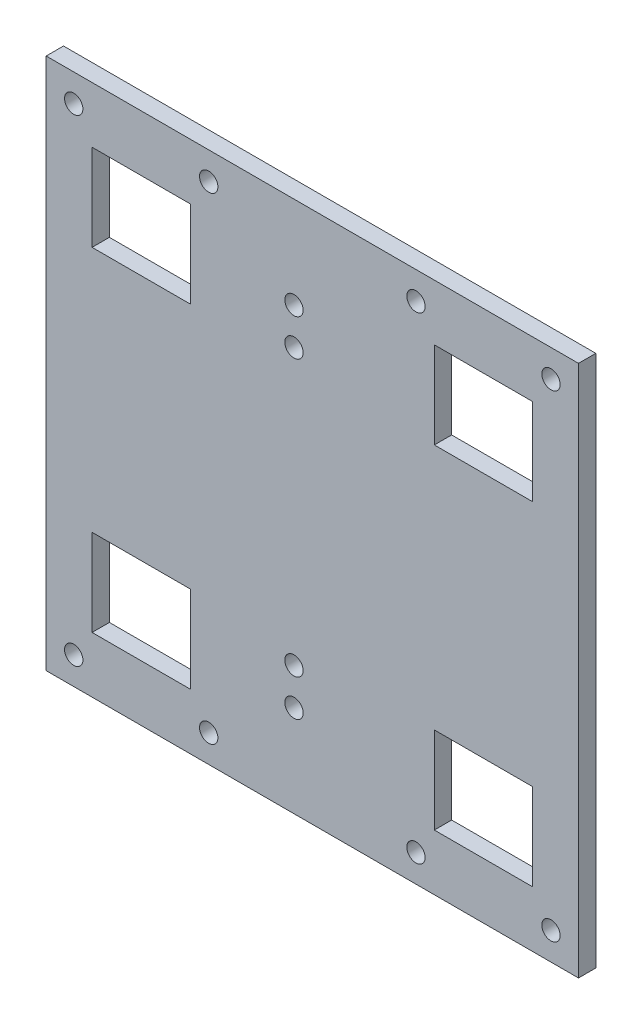
SolidWorks part; units mm, degrees
ref_plane "Front Plane" through (0, 0, 0) normal (0, 0, 1) x (1, 0, 0)
ref_plane "Top Plane" through (0, 0, 0) normal (0, 1, 0) x (1, 0, 0)
ref_plane "Right Plane" through (0, 0, 0) normal (1, 0, 0) x (0, 0, -1)
sketch "Sketch1" plane through (0, 0, 0) normal (0, 0, 1) x (1, 0, 0)
  line L0 (32.8752, 184.15) -> (32.8752, 0) construction
  line L1 (0, 0) -> (184.15, 0)
  line L2 (0, 0) -> (0, 184.15)
  line L3 (0, 184.15) -> (184.15, 184.15)
  line L4 (184.15, 0) -> (184.15, 184.15)
  line L5 (15.8752, 164.7622) -> (49.8752, 164.7622)
  line L6 (15.8752, 164.7622) -> (15.8752, 134.7622)
  line L7 (15.8752, 134.7622) -> (49.8752, 134.7622)
  line L8 (49.8752, 164.7622) -> (49.8752, 134.7622)
  line L9 (15.8752, 49.3878) -> (49.8752, 49.3878)
  line L10 (15.8752, 49.3878) -> (15.8752, 19.3878)
  line L11 (15.8752, 19.3878) -> (49.8752, 19.3878)
  line L12 (49.8752, 49.3878) -> (49.8752, 19.3878)
  line L13 (134.2748, 164.7622) -> (168.2748, 164.7622)
  line L14 (134.2748, 164.7622) -> (134.2748, 134.7622)
  line L15 (134.2748, 134.7622) -> (168.2748, 134.7622)
  line L16 (168.2748, 164.7622) -> (168.2748, 134.7622)
  line L17 (134.2748, 49.3878) -> (168.2748, 49.3878)
  line L18 (134.2748, 49.3878) -> (134.2748, 19.3878)
  line L19 (134.2748, 19.3878) -> (168.2748, 19.3878)
  line L20 (168.2748, 49.3878) -> (168.2748, 19.3878)
  line L21 (32.8752, 0) -> (151.2748, 0) construction
  line L22 (151.2748, 0) -> (151.2748, 184.15) construction
  line L23 (92.075, 184.15) -> (92.075, 0) construction
  line L25 (85.725, 152.4) -> (85.725, 139.7) construction
  circle A0 centre (9.525, 174.625) radius 3.175
  circle A1 centre (56.2254, 174.625) radius 3.175
  circle A2 centre (127.9246, 174.625) radius 3.175
  circle A3 centre (174.625, 174.625) radius 3.175
  circle A5 centre (85.725, 152.4) radius 3.175
  circle A7 centre (85.725, 139.7) radius 3.175
  circle A9 centre (9.525, 9.525) radius 3.175
  circle A10 centre (85.725, 44.45) radius 3.175
  circle A11 centre (56.2254, 9.525) radius 3.175
  circle A13 centre (85.725, 31.75) radius 3.175
  circle A14 centre (127.9246, 9.525) radius 3.175
  circle A15 centre (174.6174, 9.525) radius 3.175
  point P43 (0, 0)
  point P44 (0, 0)
  dimension "D3" = 6.35
  dimension "D20" = 12.7
  dimension "D26" = 6.35
  dimension "D1" = 184.15
  dimension "D2" = 184.15
  dimension "D4" = 34
  dimension "D5" = 30
  dimension "D6" = 46.7004
  dimension "D7" = 46.7004
  dimension "D8" = 46.6928
  dimension "D9" = 46.7004
  dimension "D10" = 9.525
  dimension "D11" = 9.525
  dimension "D12" = 9.525
  dimension "D13" = 9.525
  dimension "D14" = 32.8752
  dimension "D15" = 32.8752
  dimension "D16" = 17
  dimension "D17" = 17
  dimension "D18" = 19.3878
  dimension "D19" = 19.3878
  dimension "D21" = 6.35
  dimension "D22" = 12.7
  dimension "D23" = 31.75
  dimension "D25" = 31.75
extrude "Boss-Extrude1" add sketch "Sketch1" along normal blind 5.9944
